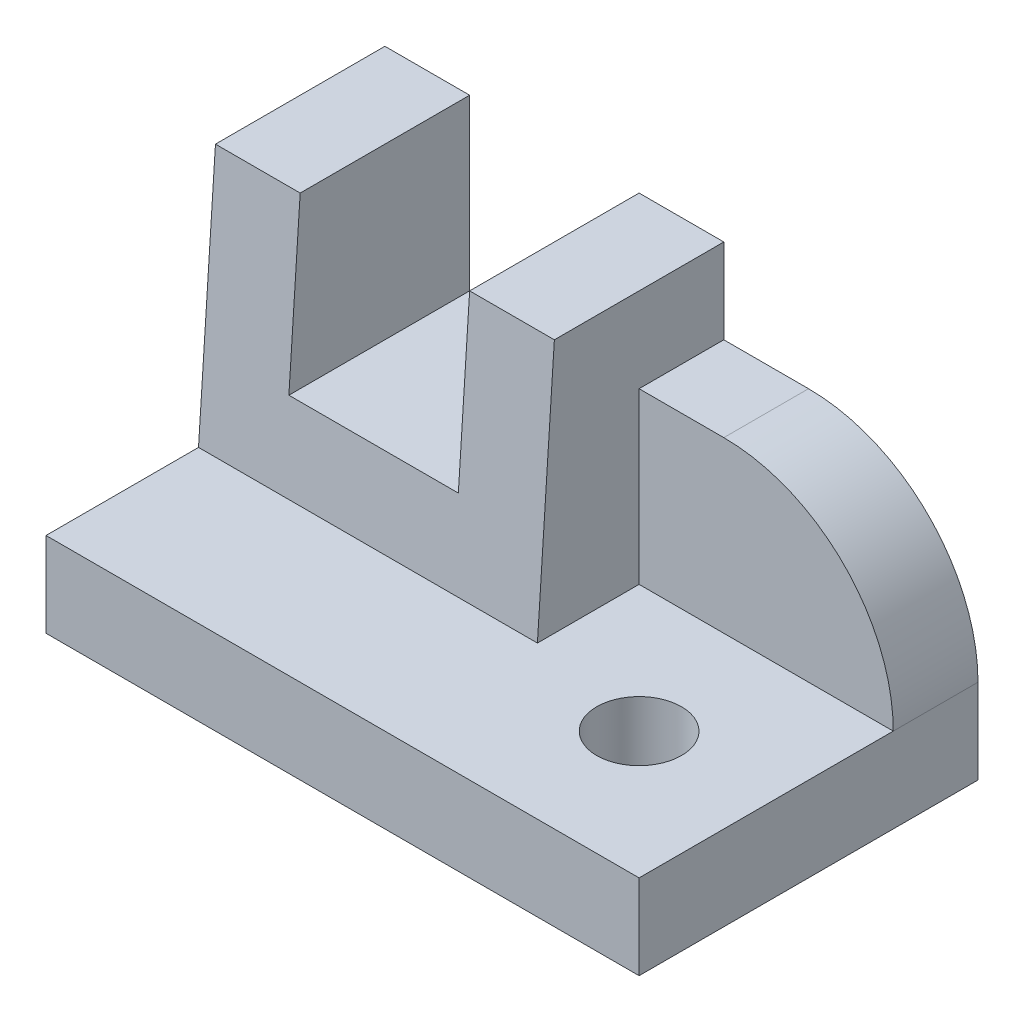
SolidWorks part; units mm, degrees
ref_plane "Front Plane" through (0, 0, 0) normal (0, 0, 1) x (1, 0, 0)
ref_plane "Top Plane" through (0, 0, 0) normal (0, 1, 0) x (1, 0, 0)
ref_plane "Right Plane" through (0, 0, 0) normal (1, 0, 0) x (0, 0, -1)
ref_plane "Plane1" through (0, 0, 0) normal (-1, 0, 0) x (0, -1, 0)
sketch "Sketch1" plane through (0, 0, 0) normal (-1, 0, 0) x (0, -1, 0)
  line L0 (-10, -18) -> (-40, -20)
  line L1 (-40, -20) -> (-10, -20)
  line L2 (-10, -20) -> (-10, -18)
  dimension "D1" = 30
  dimension "Width" = 2
extrude "Boss-Extrude1" add sketch "Sketch1" against normal blind 40
sketch "Sketch2" plane through (0, 0, -20) normal (0, 0, -1) x (-1, 0, 0)
  line L0 (-40, 40) -> (0, 40)
  line L1 (0, 40) -> (0, 10)
  line L2 (0, 10) -> (-40, 10)
  line L3 (-40, 10) -> (-40, 40)
extrude "Boss-Extrude2" add sketch "Sketch2" along normal blind 20
sketch "Sketch3" plane through (40, 0, 0) normal (1, 0, 0) x (0, 0, -1)
  line L0 (40, 10) -> (0, 10)
  line L1 (0, 10) -> (20, 40)
  line L2 (20, 40) -> (40, 40)
  line L3 (40, 40) -> (40, 10)
extrude "Boss-Extrude3" add sketch "Sketch3" along normal blind 30
sketch "Sketch4" plane through (70, 0, 0) normal (1, 0, 0) x (0, 0, -1)
  line L0 (20, 40) -> (0, 10)
  line L1 (0, 10) -> (30, 10)
  line L2 (30, 10) -> (30, 30)
  line L3 (30, 30) -> (40, 30)
  line L4 (40, 30) -> (40, 40)
  line L5 (40, 40) -> (20, 40)
extrude "Cut-Extrude1" cut sketch "Sketch4" against normal blind 30
sketch "Sketch5" plane through (0, 10, 0) normal (0, -1, 0) x (1, 0, 0)
  line L0 (70, 0) -> (70, -40)
  line L1 (70, -40) -> (0, -40)
  line L2 (0, -40) -> (0, 0)
  line L3 (0, 0) -> (70, 0)
extrude "Boss-Extrude4" add sketch "Sketch5" along normal blind 10
sketch "Sketch6" plane through (0, 0, -40) normal (0, 0, -1) x (-1, 0, 0)
  line L0 (-30, 40) -> (-30, 20)
  line L1 (-30, 20) -> (-10, 20)
  line L2 (-10, 20) -> (-10, 40)
  line L3 (-10, 40) -> (-30, 40)
extrude "Cut-Extrude2" cut sketch "Sketch6" against normal through all
hole_wizard "Ø10.0 (10) Diameter Hole1" positions "Sketch8" profile "Sketch7" hole size "Ø10.0" standard "ANSI Metric"
sketch "Sketch8" plane through (0, 0, 0) normal (0, -1, 0) x (-1, 0, 0)
  point P0 (-55, 15)
sketch "Sketch7" plane through (55, 0, -15) normal (1, 0, 0) x (0, 0, -1)
  line L0 (0, 0) -> (0, 40)
  line L1 (0, 40) -> (5, 40)
  line L2 (5, 40) -> (5, 0)
  line L5 (5, 0) -> (0, 0)
  line L11 (0, -6.35) -> (0, 107.95) construction
  dimension "Thru Hole Dia." = 10
  dimension "Thru Hole Depth" = 40
fillet "Fillet1" radius 20 1 edges at (70, 30, -35) tangent propagation no
